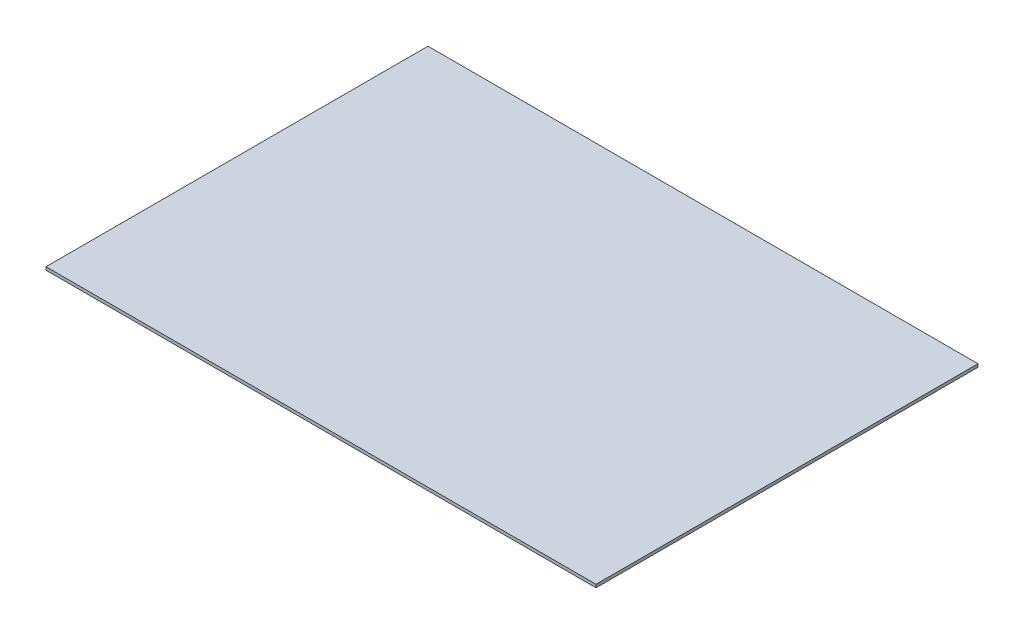
SolidWorks part; units mm, degrees
ref_plane "Alzado" through (0, 0, 0) normal (0, 0, 1) x (1, 0, 0)
ref_plane "Planta" through (0, 0, 0) normal (0, 1, 0) x (1, 0, 0)
ref_plane "Vista lateral" through (0, 0, 0) normal (1, 0, 0) x (0, 0, -1)
sketch "Croquis1" plane through (0, 0, 0) normal (0, 1, 0) x (1, 0, 0)
  line L1 (-90, -62.5) -> (90, -62.5)
  line L2 (-90, -62.5) -> (-90, 62.5)
  line L3 (-90, 62.5) -> (90, 62.5)
  line L4 (90, -62.5) -> (90, 62.5)
  line L5 (-90, -62.5) -> (90, 62.5) construction
  line L6 (-90, 62.5) -> (90, -62.5) construction
  point P0 (0, 0)
  dimension "D1" = 180
  dimension "D2" = 125
extrude "Saliente-Extruir1" add sketch "Croquis1" along normal blind 0.5 and the other way blind 0.5
